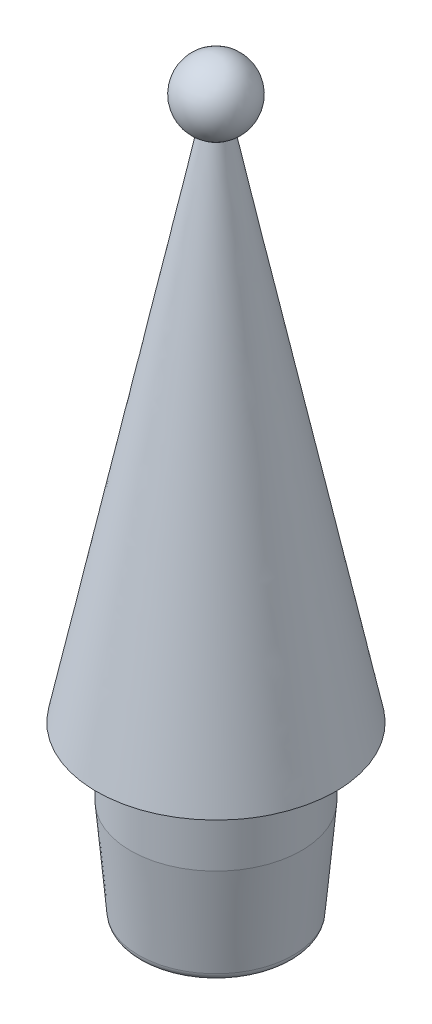
SolidWorks part; units mm, degrees
material "ABS"
ref_plane "Front Plane" through (0, 0, 0) normal (0, 0, 1) x (1, 0, 0)
ref_plane "Top Plane" through (0, 0, 0) normal (0, 1, 0) x (1, 0, 0)
ref_plane "Right Plane" through (0, 0, 0) normal (1, 0, 0) x (0, 0, -1)
sketch "Sketch1" plane through (0, 0, 0) normal (0, 1, 0) x (1, 0, 0)
  circle A0 centre (0, 0) radius 2.5
  dimension "D1" = 5
extrude "Boss-Extrude1" add sketch "Sketch1" along normal blind 5
sketch "Sketch2" plane through (0, 5, 0) normal (0, 1, 0) x (1, 0, 0)
  circle A0 centre (0, 0) radius 3.5
  dimension "D1" = 7
ref_plane "Plane1" through (0, 20, 0) normal (0, 1, 0) x (1, 0, 0)
sketch "Sketch3" plane through (0, 20, 0) normal (0, 1, 0) x (1, 0, 0)
  circle A0 centre (0, 0) radius 0.4
  circle A1 centre (0, 0) radius 0.5 construction
  circle A2 centre (0, 0) radius 0.5 construction
  point P5 (0.898, 0.638)
  point P6 (0.898, 0.638)
  dimension "D1" = 0.1
  dimension "D3" = 1
loft "Loft1" add profiles "Sketch3", "Sketch2" connector at (-0.3536, 20, -0.187) connector at (-3.3635, 5, -0.968)
sketch "Sketch4" plane through (0, 0, 0) normal (0, 1, 0) x (1, 0, 0)
  circle A0 centre (0, 0) radius 1.075
  dimension "D1" = 2.15
extrude "Cut-Extrude1" cut sketch "Sketch4" along normal blind 13 contours A0
chamfer "Chamfer1" distance 0.3 angle 88 1 edges at (0, 0, 1.075) first distance on face at (0, 0, 1.075)
chamfer "Chamfer2" distance 3 angle 5 1 edges at (0, 0, 2.5) first distance on face at (0, 5, 2.5)
fillet "Fillet2" radius 0.25 1 edges at (0, 5, 2.5)
fillet "Fillet4" radius 0.25 2 edges at (0, 0, 1.375) (0, 0, 2.2375)
sketch "Sketch5" plane through (0, 0, 0) normal (0, 0, 1) x (1, 0, 0)
  line L0 (0, 24.7272) -> (0, 0) construction
  line L1 (0, 21.9165) -> (0, 19.9165)
  line L2 (0.4, 20) -> (-0.4, 20) construction
  line L3 (0.4, 20) -> (-0.4, 20) construction
  arc A0 (0, 21.9165) -> (0, 19.9165) centre (0, 20.9165) ccw
  dimension "D1" = 1
revolve "Revolve1" add sketch "Sketch5" angle 360 about L0
sketch "Sketch6" plane through (0, 13, 0) normal (0, -1, 0) x (1, 0, 0)
  circle A0 centre (0, 0) radius 0.55
  dimension "D1" = 1.1
extrude "Cut-Extrude2" cut sketch "Sketch6" against normal blind 4 contours A0
fillet "Fillet5" radius 0.1 1 edges at (0, 13, -0.55)
